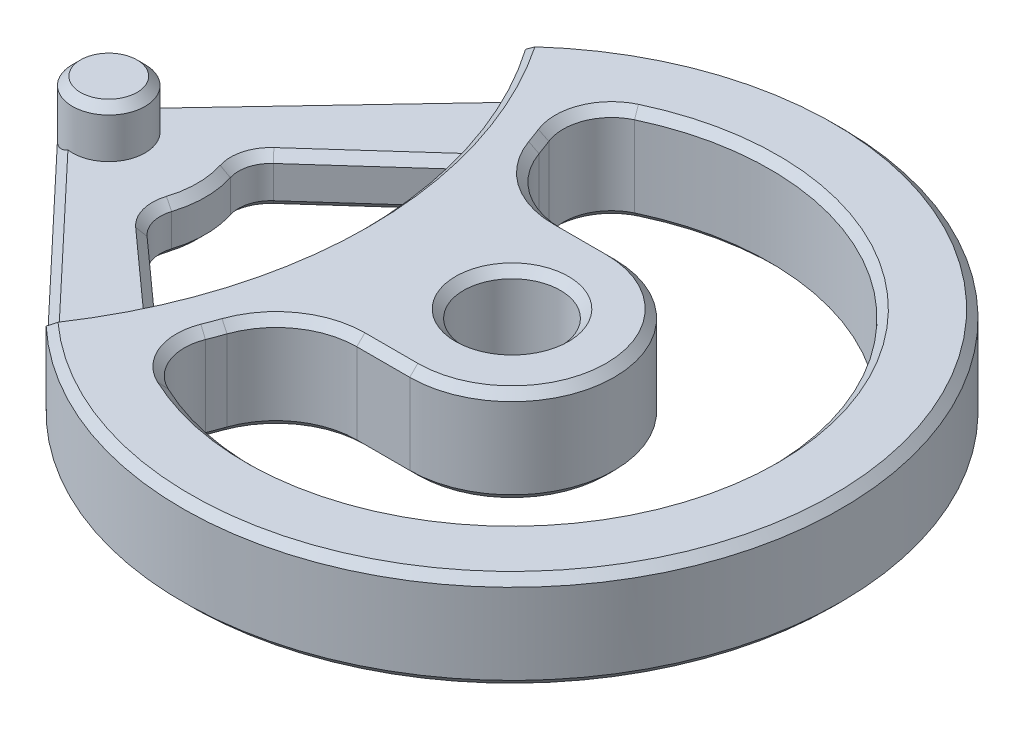
SolidWorks part; units mm, degrees
ref_plane "Front Plane" through (0, 0, 0) normal (0, 0, 1) x (1, 0, 0)
ref_plane "Top Plane" through (0, 0, 0) normal (0, 1, 0) x (1, 0, 0)
ref_plane "Right Plane" through (0, 0, 0) normal (1, 0, 0) x (0, 0, -1)
sketch "Sketch2" plane through (0, 0, 0) normal (0, 1, 0) x (1, 0, 0)
  line L1 (35.3553, 6.3391) -> (32.0707, 6.3391)
  line L2 (35.3553, -6.3391) -> (32.0707, -6.3391)
  line L3 (8.7191, 1.5445) -> (20.4986, 14.0237)
  line L4 (8.7191, -1.5445) -> (20.4986, -14.0237)
  line L5 (23.8392, -10.3776) -> (16.6424, -3.9127)
  line L6 (16.6424, 3.9127) -> (23.8392, 10.3776)
  circle A0 centre (35.3553, 0) radius 3
  arc A1 (21.335, -14.8599) -> (21.335, 14.8599) centre (0, 0) ccw
  arc A2 (20.4986, -14.0237) -> (20.4986, 14.0237) centre (35.3553, 0) ccw
  circle A3 centre (10.3553, 0) radius 2.25
  arc A4 (35.3553, -6.3391) -> (35.3553, 6.3391) centre (35.3553, 0) ccw
  arc A5 (27.3567, 9.6724) -> (26.9931, 10.645) centre (0, 0) ccw
  arc A6 (32.0707, -6.3391) -> (27.3567, -9.6724) centre (32.0707, -11.3391) ccw
  arc A7 (32.0707, 6.3391) -> (27.3567, 9.6724) centre (32.0707, 11.3391) cw
  arc A8 (26.9931, -10.645) -> (27.3567, -9.6724) centre (0, 0) ccw
  arc A9 (16.0731, -1.8187) -> (16.0731, 1.8187) centre (10.3553, 0) ccw
  arc A10 (16.0731, -1.8187) -> (16.6424, -3.9127) centre (17.979, -2.4249) ccw
  arc A11 (28.4982, -14.4561) -> (28.4982, 14.4561) centre (35.3553, 0) ccw
  arc A12 (16.0731, 1.8187) -> (16.6424, 3.9127) centre (17.979, 2.4249) cw
  arc A13 (28.4982, -14.4561) -> (26.9931, -10.645) centre (29.7839, -11.7456) cw
  arc A14 (28.4982, 14.4561) -> (26.9931, 10.645) centre (29.7839, 11.7456) ccw
  dimension "D1" = 6
  dimension "D4" = 4.5
  dimension "D3" = 5
  dimension "D5" = 12
  dimension "D6" = 2
  dimension "D7" = 32
  dimension "D8" = 3
  dimension "D9" = 26
  dimension "D2" = 25
extrude "Boss-Extrude1" add sketch "Sketch2" along normal blind 3 contours A9 A12 L6 A1 A2 L3 A3 L4 L5 A10 | A3 | A1 A2 A14 A11 A13 A8 A6 L2 A4 L1 A7 A5 A0 region at (14.8514, 0, -7.5552) region at (10.3553, 0, 0) region at (55.2509, 0, 0)
extrude "Boss-Extrude2" add sketch "Sketch2<5>" along normal blind 6 contours A2 A1 A0 | A3 region at (10.3553, 0, 0) region at (55.2509, 0, 0)
sketch "Sketch2<5>" plane through (0, 0, 0) normal (0, 1, 0) x (1, 0, 0) same geometry as "Sketch2"
chamfer "Chamfer1" distance 0.5 angle 45 44 edges at (55.7853, 6, 0) (26, 6, 0) (20.2408, 3, 7.1452) (16.049, 3, 2.9496) (16.3553, 3, 0) (16.049, 3, -2.9496) (20.2408, 3, -7.1452) (20.9108, 3, -14.4478) (14.6089, 3, -7.7841) (20.9108, 3, 14.4478) (14.6089, 3, 7.7841) (10.3553, 6, 2.25) (20.2408, 0, 7.1452) (16.049, 0, 2.9496) (16.3553, 0, 0) (16.049, 0, -2.9496) (20.2408, 0, -7.1452) (26, 0, 0) (55.7853, 0, 0) (14.6089, 0, -7.7841) (8.1053, 0, 0) (14.6089, 0, 7.7841) (33.713, 6, -6.3391) (29.184, 6, -7.2566) (27.1792, 6, -10.1603) (26.9936, 6, -12.8476) (51.3553, 6, 0) (26.9936, 6, 12.8476) (27.1792, 6, 10.1603) (29.184, 6, 7.2566) (33.713, 6, 6.3391) (41.6944, 6, 0) (35.3553, 6, 3) (33.713, 0, 6.3391) (29.184, 0, 7.2566) (27.1792, 0, 10.1603) (26.9936, 0, 12.8476) (51.3553, 0, 0) (26.9936, 0, -12.8476) (27.1792, 0, -10.1603) (29.184, 0, -7.2566) (33.713, 0, -6.3391) (41.6944, 0, 0) (35.3553, 0, 3)
